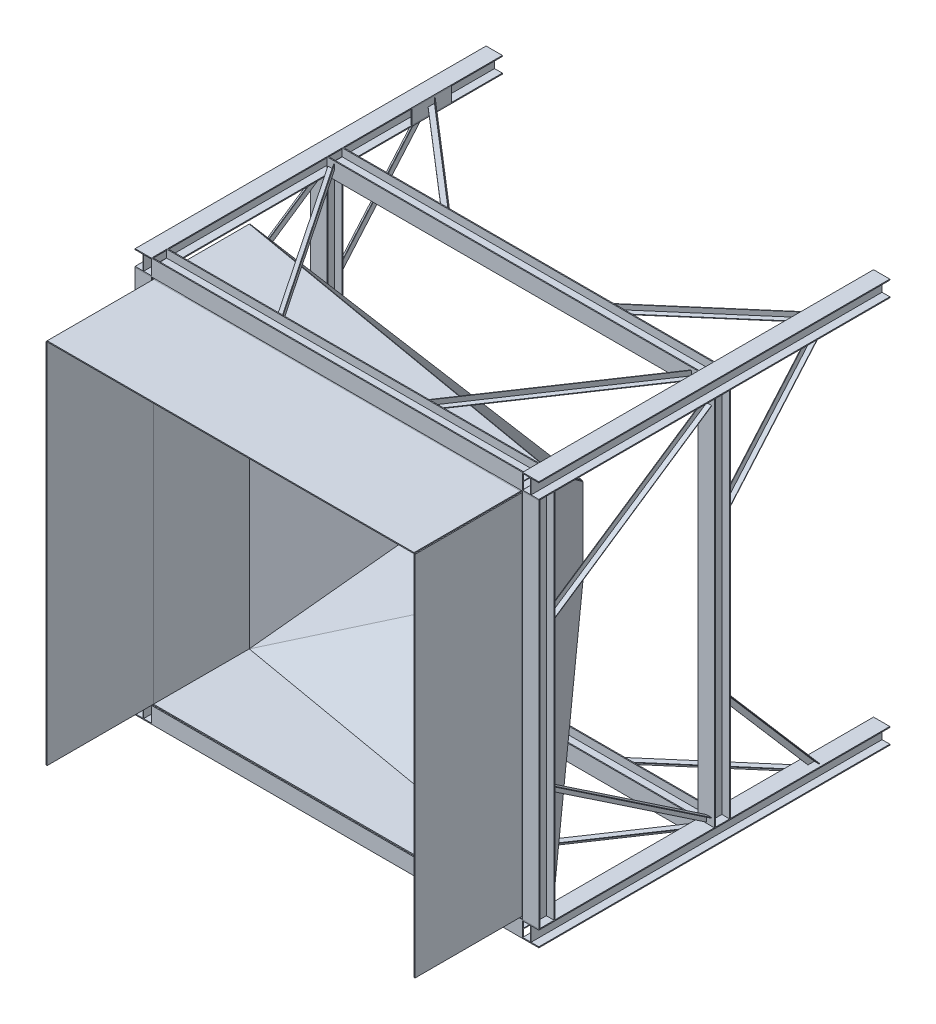
SolidWorks part; units mm, degrees
other "DetailItem1"
other "DetailItem2"
other "DetailItem3"
other "DetailItem4"
other "DetailItem5"
other "DetailItem6"
other "DetailItem7"
other "DetailItem8"
other "DetailItem9"
other "DetailItem10"
other "DetailItem11"
other "DetailItem12"
other "DetailItem13"
other "DetailItem14"
other "DetailItem15"
other "DetailItem16"
other "DetailItem17"
other "DetailItem18"
other "DetailItem19"
other "DetailItem20"
other "DetailItem21"
other "DetailItem22"
other "DetailItem23"
other "DetailItem24"
other "DetailItem25"
other "DetailItem26"
other "DetailItem27"
other "DetailItem28"
other "DetailItem29"
other "DetailItem30"
other "DetailItem31"
other "DetailItem32"
other "DetailItem33"
other "DetailItem34"
other "DetailItem35"
other "DetailItem36"
other "DetailItem37"
other "DetailItem38"
other "DetailItem39"
other "DetailItem40"
other "DetailItem41"
other "DetailItem42"
other "DetailItem43"
other "DetailItem44"
other "DetailItem45"
other "DetailItem46"
other "DetailItem47"
other "DetailItem48"
other "DetailItem49"
other "DetailItem50"
other "DetailItem51"
other "DetailItem52"
other "DetailItem53"
other "DetailItem54"
other "DetailItem55"
other "DetailItem56"
other "DetailItem57"
other "DetailItem58"
other "DetailItem59"
other "DetailItem60"
other "DetailItem61"
other "DetailItem62"
other "DetailItem63"
other "DetailItem64"
other "DetailItem65"
other "DetailItem66"
other "DetailItem67"
other "DetailItem68"
other "DetailItem69"
other "DetailItem70"
other "DetailItem71"
other "DetailItem72"
other "DetailItem73"
other "DetailItem74"
other "DetailItem75"
other "Carpeta de soldadura"
other "Cordón de soldadura1"
other "Soldadura Viga H carga 1650 B"
other "Soldadura Viga H carga 3300 A"
other "Soldadura Viga H carga 3300 B"
other "Soldadura asiento a tolva carga"
other "Soldadura asiento a bastidor carga"
other "Soldadura Viga H fondo 1650 A"
other "Soldadura Viga H fondo 1650 B"
other "Soldadura Viga H fondo 3300 A"
other "Soldadura Viga H fondo 3300 B"
other "Soldadura asiento a tolva fondo"
other "Soldadura asiento a bastidor fondo"
other "Soldadura Viga H izquierda 1650 A"
other "Soldadura Viga H izquierda 1650 B"
other "Soldadura Viga H izquierda 3300 A"
other "Soldadura Viga H izquierda 3300 B"
other "Soldadura asiento a tolva izquierda"
other "Soldadura asiento a bastidor izquierda"
other "Soldadura Viga H derecha 1650 A"
other "Soldadura Viga H derecha 1650 B"
other "Soldadura Viga H derecha 3300 A"
other "Soldadura Viga H derecha 3300 B"
other "Soldadura asiento a tolva derecha"
other "Soldadura asiento a bastidor derecha"
other "Soldadura Angular superior carga A inferior"
other "Soldadura Angular superior carga A superior"
other "Soldadura Angular inferior carga A inferior"
other "Soldadura Angular inferior carga A superior"
other "Soldadura Angular superior carga B inferior"
other "Soldadura Angular superior carga B superior"
other "Soldadura Angular inferior carga B inferior"
other "Soldadura Angular inferior carga B superior"
other "Soldadura Angular superior fondo A inferior"
other "Soldadura Angular superior fondo A superior"
other "Soldadura Angular inferior fondo A inferior"
other "Soldadura Angular inferior fondo A superior"
other "Soldadura Angular superior fondo B inferior"
other "Soldadura Angular superior fondo B superior"
other "Soldadura Angular inferior fondo B inferior"
other "Soldadura Angular inferior fondo B superior"
other "Soldadura Angular superior izquierda A inferior"
other "Soldadura Angular superior izquierda A superior"
other "Soldadura Angular inferior izquierda A inferior"
other "Soldadura Angular inferior izquierda A superior"
other "Soldadura Angular superior izquierda B inferior"
other "Soldadura Angular superior izquierda B superior"
other "Soldadura Angular inferior izquierda B inferior"
other "Soldadura Angular inferior izquierda B superior"
other "Soldadura Angular superior derecha A inferior"
other "Soldadura Angular superior derecha A superior"
other "Soldadura Angular inferior derecha A inferior"
other "Soldadura Angular inferior derecha A superior"
other "Soldadura Angular superior derecha B inferior"
other "Soldadura Angular superior derecha B superior"
other "Soldadura Angular inferior derecha B inferior"
other "Soldadura Angular inferior derecha B superior"
other "Soldadura esquina del collar carga"
other "Soldadura quiebre del embudo carga"
other "Soldadura arista inclinada carga"
other "Soldadura diagonal carga"
other "Soldadura alerón a collar derecha"
other "Soldadura esquina del collar derecha"
other "Soldadura quiebre del embudo derecha"
other "Soldadura arista inclinada derecha"
other "Soldadura alerón a collar fondo"
other "Soldadura esquina del collar fondo"
other "Soldadura quiebre del embudo fondo"
other "Soldadura arista inclinada fondo"
other "Soldadura diagonal fondo"
other "Soldadura alerón a collar izquierda"
other "Soldadura esquina del collar izquierda"
other "Soldadura quiebre del embudo izquierda"
other "Soldadura arista inclinada izquierda"
other "Soldadura esquina alerones derecha"
other "Soldadura esquina alerones izquierda"
material "ASTM A36 Steel"
ref_plane "Front Plane" through (0, 0, 0) normal (0, 0, 1) x (1, 0, 0)
ref_plane "Top Plane" through (0, 0, 0) normal (0, 1, 0) x (1, 0, 0)
ref_plane "Right Plane" through (0, 0, 0) normal (1, 0, 0) x (0, 0, -1)
sketch3d "Referencias 1"
  point P0 (0, 0, 0)
  point P1 (0, -190, 0)
  point P2 (200, 0, 0)
ref_plane "Plano de perfil 1 estructura" through (0, 0, 0) normal (0, 0, 1) x (1, 0, 0)
sketch "Contorno Columna H 1" plane through (0, 0, 0) normal (0, 0, 1) x (1, 0, 0)
  line L0 (-1898, -1898) -> (-1745, -1898)
  line L1 (-1745, -1898) -> (-1745, -1889)
  line L2 (-1745, -1889) -> (-1818.25, -1889)
  line L3 (-1818.25, -1889) -> (-1818.25, -1754)
  line L4 (-1818.25, -1754) -> (-1745, -1754)
  line L5 (-1745, -1754) -> (-1745, -1745)
  line L6 (-1745, -1745) -> (-1898, -1745)
  line L7 (-1898, -1745) -> (-1898, -1754)
  line L8 (-1898, -1754) -> (-1824.75, -1754)
  line L9 (-1824.75, -1754) -> (-1824.75, -1889)
  line L10 (-1824.75, -1889) -> (-1898, -1889)
  line L11 (-1898, -1889) -> (-1898, -1898)
extrude "Columna H 1" add sketch "Contorno Columna H 1" along normal blind 3300 separate body
sketch "Contorno Columna H 2" plane through (0, 0, 0) normal (0, 0, 1) x (1, 0, 0)
  line L0 (-1898, 1745) -> (-1745, 1745)
  line L1 (-1745, 1745) -> (-1745, 1754)
  line L2 (-1745, 1754) -> (-1818.25, 1754)
  line L3 (-1818.25, 1754) -> (-1818.25, 1889)
  line L4 (-1818.25, 1889) -> (-1745, 1889)
  line L5 (-1745, 1889) -> (-1745, 1898)
  line L6 (-1745, 1898) -> (-1898, 1898)
  line L7 (-1898, 1898) -> (-1898, 1889)
  line L8 (-1898, 1889) -> (-1824.75, 1889)
  line L9 (-1824.75, 1889) -> (-1824.75, 1754)
  line L10 (-1824.75, 1754) -> (-1898, 1754)
  line L11 (-1898, 1754) -> (-1898, 1745)
extrude "Columna H 2" add sketch "Contorno Columna H 2" along normal blind 3300 separate body
sketch "Contorno Columna H 3" plane through (0, 0, 0) normal (0, 0, 1) x (1, 0, 0)
  line L0 (1745, -1898) -> (1898, -1898)
  line L1 (1898, -1898) -> (1898, -1889)
  line L2 (1898, -1889) -> (1824.75, -1889)
  line L3 (1824.75, -1889) -> (1824.75, -1754)
  line L4 (1824.75, -1754) -> (1898, -1754)
  line L5 (1898, -1754) -> (1898, -1745)
  line L6 (1898, -1745) -> (1745, -1745)
  line L7 (1745, -1745) -> (1745, -1754)
  line L8 (1745, -1754) -> (1818.25, -1754)
  line L9 (1818.25, -1754) -> (1818.25, -1889)
  line L10 (1818.25, -1889) -> (1745, -1889)
  line L11 (1745, -1889) -> (1745, -1898)
extrude "Columna H 3" add sketch "Contorno Columna H 3" along normal blind 3300 separate body
sketch "Contorno Columna H 4" plane through (0, 0, 0) normal (0, 0, 1) x (1, 0, 0)
  line L0 (1745, 1745) -> (1898, 1745)
  line L1 (1898, 1745) -> (1898, 1754)
  line L2 (1898, 1754) -> (1824.75, 1754)
  line L3 (1824.75, 1754) -> (1824.75, 1889)
  line L4 (1824.75, 1889) -> (1898, 1889)
  line L5 (1898, 1889) -> (1898, 1898)
  line L6 (1898, 1898) -> (1745, 1898)
  line L7 (1745, 1898) -> (1745, 1889)
  line L8 (1745, 1889) -> (1818.25, 1889)
  line L9 (1818.25, 1889) -> (1818.25, 1754)
  line L10 (1818.25, 1754) -> (1745, 1754)
  line L11 (1745, 1754) -> (1745, 1745)
extrude "Columna H 4" add sketch "Contorno Columna H 4" along normal blind 3300 separate body
sketch3d "Referencias 2"
  point P0 (-1745, 0, 0)
  point P1 (-1745, 190, 0)
  point P2 (-1745, 0, 200)
ref_plane "Plano de perfil 2 estructura" through (-1745, 0, 0) normal (1, 0, 0) x (0, 0, -1)
sketch "Contorno Viga H carga 1650" plane through (-1745, 0, 0) normal (1, 0, 0) x (0, 0, -1)
  line L0 (-1497, -1745) -> (-1497, -1898)
  line L1 (-1497, -1898) -> (-1506, -1898)
  line L2 (-1506, -1898) -> (-1506, -1824.75)
  line L3 (-1506, -1824.75) -> (-1641, -1824.75)
  line L4 (-1641, -1824.75) -> (-1641, -1898)
  line L5 (-1641, -1898) -> (-1650, -1898)
  line L6 (-1650, -1898) -> (-1650, -1745)
  line L7 (-1650, -1745) -> (-1641, -1745)
  line L8 (-1641, -1745) -> (-1641, -1818.25)
  line L9 (-1641, -1818.25) -> (-1506, -1818.25)
  line L10 (-1506, -1818.25) -> (-1506, -1745)
  line L11 (-1506, -1745) -> (-1497, -1745)
extrude "Viga H carga 1650" add sketch "Contorno Viga H carga 1650" along normal blind 3490 separate body
sketch "Contorno Viga H carga 3300" plane through (-1745, 0, 0) normal (1, 0, 0) x (0, 0, -1)
  line L0 (-3147, -1745) -> (-3147, -1898)
  line L1 (-3147, -1898) -> (-3156, -1898)
  line L2 (-3156, -1898) -> (-3156, -1824.75)
  line L3 (-3156, -1824.75) -> (-3291, -1824.75)
  line L4 (-3291, -1824.75) -> (-3291, -1898)
  line L5 (-3291, -1898) -> (-3300, -1898)
  line L6 (-3300, -1898) -> (-3300, -1745)
  line L7 (-3300, -1745) -> (-3291, -1745)
  line L8 (-3291, -1745) -> (-3291, -1818.25)
  line L9 (-3291, -1818.25) -> (-3156, -1818.25)
  line L10 (-3156, -1818.25) -> (-3156, -1745)
  line L11 (-3156, -1745) -> (-3147, -1745)
extrude "Viga H carga 3300" add sketch "Contorno Viga H carga 3300" along normal blind 3490 separate body
sketch "Contorno Cierre columna carga A" plane through (-1745, 0, 0) normal (1, 0, 0) x (0, 0, -1)
  line L0 (-480, -1754) -> (-480, -1889)
  line L1 (-480, -1889) -> (-850, -1889)
  line L2 (-850, -1889) -> (-850, -1754)
  line L3 (-850, -1754) -> (-480, -1754)
extrude "Cierre columna carga A" add sketch "Contorno Cierre columna carga A" against normal blind 8 separate body
sketch3d "Referencias 3"
  point P0 (0, -1821.5, 0)
  point P1 (-190, -1821.5, 0)
  point P2 (0, -1821.5, 200)
ref_plane "Plano de perfil 3 estructura" through (0, -1821.5, 0) normal (0, 1, 0) x (1, 0, 0)
sketch "Contorno Ala plana Angular superior carga A" plane through (0, -1821.5, 0) normal (0, 1, 0) x (1, 0, 0)
  line L0 (-1674.8701, -1650) -> (-1735.1299, -1650)
  line L1 (-1735.1299, -1650) -> (-728.1299, -3147)
  line L2 (-728.1299, -3147) -> (-667.8701, -3147)
  line L3 (-667.8701, -3147) -> (-1674.8701, -1650)
extrude "Ala plana Angular superior carga A" add sketch "Contorno Ala plana Angular superior carga A" against normal blind 5 separate body
sketch3d "Referencias 4"
  point P0 (0, -1826.5, 0)
  point P1 (-190, -1826.5, 0)
  point P2 (0, -1826.5, 200)
ref_plane "Plano de perfil 4 estructura" through (0, -1826.5, 0) normal (0, 1, 0) x (1, 0, 0)
sketch "Contorno Retorno Angular superior carga A" plane through (0, -1826.5, 0) normal (0, 1, 0) x (1, 0, 0)
  line L0 (-1674.8701, -1650) -> (-1680.8961, -1650)
  line L1 (-1680.8961, -1650) -> (-673.8961, -3147)
  line L2 (-673.8961, -3147) -> (-667.8701, -3147)
  line L3 (-667.8701, -3147) -> (-1674.8701, -1650)
extrude "Retorno Angular superior carga A" add sketch "Contorno Retorno Angular superior carga A" against normal blind 45 separate body
combine bodies "Angular superior carga A" operation type add bodies to combine 108 109
sketch "Contorno Ala plana Angular inferior carga A" plane through (0, -1821.5, 0) normal (0, 1, 0) x (1, 0, 0)
  line L0 (-1745, -631.991) -> (-1745, -698.009)
  line L1 (-1745, -698.009) -> (-818.2856, -1497)
  line L2 (-818.2856, -1497) -> (-741.7144, -1497)
  line L3 (-741.7144, -1497) -> (-1745, -631.991)
extrude "Ala plana Angular inferior carga A" add sketch "Contorno Ala plana Angular inferior carga A" against normal blind 5 separate body
sketch "Contorno Retorno Angular inferior carga A" plane through (0, -1826.5, 0) normal (0, 1, 0) x (1, 0, 0)
  line L0 (-1745, -631.991) -> (-1745, -638.5928)
  line L1 (-1745, -638.5928) -> (-749.3715, -1497)
  line L2 (-749.3715, -1497) -> (-741.7144, -1497)
  line L3 (-741.7144, -1497) -> (-1745, -631.991)
extrude "Retorno Angular inferior carga A" add sketch "Contorno Retorno Angular inferior carga A" against normal blind 45 separate body
combine bodies "Angular inferior carga A" operation type add bodies to combine 111 112
sketch3d "Referencias 5"
  point P0 (1745, 0, 0)
  point P1 (1745, 190, 0)
  point P2 (1745, 0, 200)
ref_plane "Plano de perfil 5 estructura" through (1745, 0, 0) normal (1, 0, 0) x (0, 0, -1)
sketch "Contorno Cierre columna carga B" plane through (1745, 0, 0) normal (1, 0, 0) x (0, 0, -1)
  line L0 (-480, -1754) -> (-480, -1889)
  line L1 (-480, -1889) -> (-850, -1889)
  line L2 (-850, -1889) -> (-850, -1754)
  line L3 (-850, -1754) -> (-480, -1754)
extrude "Cierre columna carga B" add sketch "Contorno Cierre columna carga B" along normal blind 8 separate body
sketch "Contorno Ala plana Angular superior carga B" plane through (0, -1821.5, 0) normal (0, 1, 0) x (1, 0, 0)
  line L0 (1674.8701, -1650) -> (1735.1299, -1650)
  line L1 (1735.1299, -1650) -> (728.1299, -3147)
  line L2 (728.1299, -3147) -> (667.8701, -3147)
  line L3 (667.8701, -3147) -> (1674.8701, -1650)
extrude "Ala plana Angular superior carga B" add sketch "Contorno Ala plana Angular superior carga B" against normal blind 5 separate body
sketch "Contorno Retorno Angular superior carga B" plane through (0, -1826.5, 0) normal (0, 1, 0) x (1, 0, 0)
  line L0 (1674.8701, -1650) -> (1680.8961, -1650)
  line L1 (1680.8961, -1650) -> (673.8961, -3147)
  line L2 (673.8961, -3147) -> (667.8701, -3147)
  line L3 (667.8701, -3147) -> (1674.8701, -1650)
extrude "Retorno Angular superior carga B" add sketch "Contorno Retorno Angular superior carga B" against normal blind 45 separate body
combine bodies "Angular superior carga B" operation type add bodies to combine 115 116
sketch "Contorno Ala plana Angular inferior carga B" plane through (0, -1821.5, 0) normal (0, 1, 0) x (1, 0, 0)
  line L0 (1745, -631.991) -> (1745, -698.009)
  line L1 (1745, -698.009) -> (818.2856, -1497)
  line L2 (818.2856, -1497) -> (741.7144, -1497)
  line L3 (741.7144, -1497) -> (1745, -631.991)
extrude "Ala plana Angular inferior carga B" add sketch "Contorno Ala plana Angular inferior carga B" against normal blind 5 separate body
sketch "Contorno Retorno Angular inferior carga B" plane through (0, -1826.5, 0) normal (0, 1, 0) x (1, 0, 0)
  line L0 (1745, -631.991) -> (1745, -638.5928)
  line L1 (1745, -638.5928) -> (749.3715, -1497)
  line L2 (749.3715, -1497) -> (741.7144, -1497)
  line L3 (741.7144, -1497) -> (1745, -631.991)
extrude "Retorno Angular inferior carga B" add sketch "Contorno Retorno Angular inferior carga B" against normal blind 45 separate body
combine bodies "Angular inferior carga B" operation type add bodies to combine 118 119
sketch3d "Referencias 6"
  point P0 (0, 0, 3281.475)
  point P1 (0, -190, 3281.475)
  point P2 (200, 0, 3281.475)
ref_plane "Plano de perfil 6 estructura" through (0, 0, 3281.475) normal (0, 0, 1) x (1, 0, 0)
sketch "Contorno Asiento soldado carga" plane through (0, 0, 3281.475) normal (0, 0, 1) x (1, 0, 0)
  line L0 (-1450, -1734.525) -> (1450, -1734.525)
  line L1 (1450, -1734.525) -> (1450, -1818.25)
  line L2 (1450, -1818.25) -> (-1450, -1818.25)
  line L3 (-1450, -1818.25) -> (-1450, -1734.525)
extrude "Asiento soldado carga" add sketch "Contorno Asiento soldado carga" along normal blind 9.525 separate body
sketch "Contorno Viga H fondo 1650" plane through (-1745, 0, 0) normal (1, 0, 0) x (0, 0, -1)
  line L0 (-1497, 1745) -> (-1497, 1898)
  line L1 (-1497, 1898) -> (-1506, 1898)
  line L2 (-1506, 1898) -> (-1506, 1824.75)
  line L3 (-1506, 1824.75) -> (-1641, 1824.75)
  line L4 (-1641, 1824.75) -> (-1641, 1898)
  line L5 (-1641, 1898) -> (-1650, 1898)
  line L6 (-1650, 1898) -> (-1650, 1745)
  line L7 (-1650, 1745) -> (-1641, 1745)
  line L8 (-1641, 1745) -> (-1641, 1818.25)
  line L9 (-1641, 1818.25) -> (-1506, 1818.25)
  line L10 (-1506, 1818.25) -> (-1506, 1745)
  line L11 (-1506, 1745) -> (-1497, 1745)
extrude "Viga H fondo 1650" add sketch "Contorno Viga H fondo 1650" along normal blind 3490 separate body
sketch "Contorno Viga H fondo 3300" plane through (-1745, 0, 0) normal (1, 0, 0) x (0, 0, -1)
  line L0 (-3147, 1745) -> (-3147, 1898)
  line L1 (-3147, 1898) -> (-3156, 1898)
  line L2 (-3156, 1898) -> (-3156, 1824.75)
  line L3 (-3156, 1824.75) -> (-3291, 1824.75)
  line L4 (-3291, 1824.75) -> (-3291, 1898)
  line L5 (-3291, 1898) -> (-3300, 1898)
  line L6 (-3300, 1898) -> (-3300, 1745)
  line L7 (-3300, 1745) -> (-3291, 1745)
  line L8 (-3291, 1745) -> (-3291, 1818.25)
  line L9 (-3291, 1818.25) -> (-3156, 1818.25)
  line L10 (-3156, 1818.25) -> (-3156, 1745)
  line L11 (-3156, 1745) -> (-3147, 1745)
extrude "Viga H fondo 3300" add sketch "Contorno Viga H fondo 3300" along normal blind 3490 separate body
sketch "Contorno Cierre columna fondo A" plane through (-1745, 0, 0) normal (1, 0, 0) x (0, 0, -1)
  line L0 (-480, 1754) -> (-480, 1889)
  line L1 (-480, 1889) -> (-850, 1889)
  line L2 (-850, 1889) -> (-850, 1754)
  line L3 (-850, 1754) -> (-480, 1754)
extrude "Cierre columna fondo A" add sketch "Contorno Cierre columna fondo A" against normal blind 8 separate body
sketch3d "Referencias 7"
  point P0 (0, 1821.5, 0)
  point P1 (-190, 1821.5, 0)
  point P2 (0, 1821.5, 200)
ref_plane "Plano de perfil 7 estructura" through (0, 1821.5, 0) normal (0, 1, 0) x (1, 0, 0)
sketch "Contorno Ala plana Angular superior fondo A" plane through (0, 1821.5, 0) normal (0, 1, 0) x (1, 0, 0)
  line L0 (-1674.8701, -1650) -> (-1735.1299, -1650)
  line L1 (-1735.1299, -1650) -> (-728.1299, -3147)
  line L2 (-728.1299, -3147) -> (-667.8701, -3147)
  line L3 (-667.8701, -3147) -> (-1674.8701, -1650)
extrude "Ala plana Angular superior fondo A" add sketch "Contorno Ala plana Angular superior fondo A" along normal blind 5 separate body
sketch3d "Referencias 8"
  point P0 (0, 1826.5, 0)
  point P1 (-190, 1826.5, 0)
  point P2 (0, 1826.5, 200)
ref_plane "Plano de perfil 8 estructura" through (0, 1826.5, 0) normal (0, 1, 0) x (1, 0, 0)
sketch "Contorno Retorno Angular superior fondo A" plane through (0, 1826.5, 0) normal (0, 1, 0) x (1, 0, 0)
  line L0 (-1674.8701, -1650) -> (-1680.8961, -1650)
  line L1 (-1680.8961, -1650) -> (-673.8961, -3147)
  line L2 (-673.8961, -3147) -> (-667.8701, -3147)
  line L3 (-667.8701, -3147) -> (-1674.8701, -1650)
extrude "Retorno Angular superior fondo A" add sketch "Contorno Retorno Angular superior fondo A" along normal blind 45 separate body
combine bodies "Angular superior fondo A" operation type add bodies to combine 125 126
sketch "Contorno Ala plana Angular inferior fondo A" plane through (0, 1821.5, 0) normal (0, 1, 0) x (1, 0, 0)
  line L0 (-1745, -631.991) -> (-1745, -698.009)
  line L1 (-1745, -698.009) -> (-818.2856, -1497)
  line L2 (-818.2856, -1497) -> (-741.7144, -1497)
  line L3 (-741.7144, -1497) -> (-1745, -631.991)
extrude "Ala plana Angular inferior fondo A" add sketch "Contorno Ala plana Angular inferior fondo A" along normal blind 5 separate body
sketch "Contorno Retorno Angular inferior fondo A" plane through (0, 1826.5, 0) normal (0, 1, 0) x (1, 0, 0)
  line L0 (-1745, -631.991) -> (-1745, -638.5928)
  line L1 (-1745, -638.5928) -> (-749.3715, -1497)
  line L2 (-749.3715, -1497) -> (-741.7144, -1497)
  line L3 (-741.7144, -1497) -> (-1745, -631.991)
extrude "Retorno Angular inferior fondo A" add sketch "Contorno Retorno Angular inferior fondo A" along normal blind 45 separate body
combine bodies "Angular inferior fondo A" operation type add bodies to combine 128 129
sketch "Contorno Cierre columna fondo B" plane through (1745, 0, 0) normal (1, 0, 0) x (0, 0, -1)
  line L0 (-480, 1754) -> (-480, 1889)
  line L1 (-480, 1889) -> (-850, 1889)
  line L2 (-850, 1889) -> (-850, 1754)
  line L3 (-850, 1754) -> (-480, 1754)
extrude "Cierre columna fondo B" add sketch "Contorno Cierre columna fondo B" along normal blind 8 separate body
sketch "Contorno Ala plana Angular superior fondo B" plane through (0, 1821.5, 0) normal (0, 1, 0) x (1, 0, 0)
  line L0 (1674.8701, -1650) -> (1735.1299, -1650)
  line L1 (1735.1299, -1650) -> (728.1299, -3147)
  line L2 (728.1299, -3147) -> (667.8701, -3147)
  line L3 (667.8701, -3147) -> (1674.8701, -1650)
extrude "Ala plana Angular superior fondo B" add sketch "Contorno Ala plana Angular superior fondo B" along normal blind 5 separate body
sketch "Contorno Retorno Angular superior fondo B" plane through (0, 1826.5, 0) normal (0, 1, 0) x (1, 0, 0)
  line L0 (1674.8701, -1650) -> (1680.8961, -1650)
  line L1 (1680.8961, -1650) -> (673.8961, -3147)
  line L2 (673.8961, -3147) -> (667.8701, -3147)
  line L3 (667.8701, -3147) -> (1674.8701, -1650)
extrude "Retorno Angular superior fondo B" add sketch "Contorno Retorno Angular superior fondo B" along normal blind 45 separate body
combine bodies "Angular superior fondo B" operation type add bodies to combine 132 133
sketch "Contorno Ala plana Angular inferior fondo B" plane through (0, 1821.5, 0) normal (0, 1, 0) x (1, 0, 0)
  line L0 (1745, -631.991) -> (1745, -698.009)
  line L1 (1745, -698.009) -> (818.2856, -1497)
  line L2 (818.2856, -1497) -> (741.7144, -1497)
  line L3 (741.7144, -1497) -> (1745, -631.991)
extrude "Ala plana Angular inferior fondo B" add sketch "Contorno Ala plana Angular inferior fondo B" along normal blind 5 separate body
sketch "Contorno Retorno Angular inferior fondo B" plane through (0, 1826.5, 0) normal (0, 1, 0) x (1, 0, 0)
  line L0 (1745, -631.991) -> (1745, -638.5928)
  line L1 (1745, -638.5928) -> (749.3715, -1497)
  line L2 (749.3715, -1497) -> (741.7144, -1497)
  line L3 (741.7144, -1497) -> (1745, -631.991)
extrude "Retorno Angular inferior fondo B" add sketch "Contorno Retorno Angular inferior fondo B" along normal blind 45 separate body
combine bodies "Angular inferior fondo B" operation type add bodies to combine 135 136
sketch "Contorno Asiento soldado fondo" plane through (0, 0, 3281.475) normal (0, 0, 1) x (1, 0, 0)
  line L0 (-1450, 1734.525) -> (1450, 1734.525)
  line L1 (1450, 1734.525) -> (1450, 1818.25)
  line L2 (1450, 1818.25) -> (-1450, 1818.25)
  line L3 (-1450, 1818.25) -> (-1450, 1734.525)
extrude "Asiento soldado fondo" add sketch "Contorno Asiento soldado fondo" along normal blind 9.525 separate body
sketch3d "Referencias 9"
  point P0 (0, -1745, 0)
  point P1 (-190, -1745, 0)
  point P2 (0, -1745, 200)
ref_plane "Plano de perfil 9 estructura" through (0, -1745, 0) normal (0, 1, 0) x (1, 0, 0)
sketch "Contorno Viga H izquierda 1650" plane through (0, -1745, 0) normal (0, 1, 0) x (1, 0, 0)
  line L0 (-1745, -1497) -> (-1898, -1497)
  line L1 (-1898, -1497) -> (-1898, -1506)
  line L2 (-1898, -1506) -> (-1824.75, -1506)
  line L3 (-1824.75, -1506) -> (-1824.75, -1641)
  line L4 (-1824.75, -1641) -> (-1898, -1641)
  line L5 (-1898, -1641) -> (-1898, -1650)
  line L6 (-1898, -1650) -> (-1745, -1650)
  line L7 (-1745, -1650) -> (-1745, -1641)
  line L8 (-1745, -1641) -> (-1818.25, -1641)
  line L9 (-1818.25, -1641) -> (-1818.25, -1506)
  line L10 (-1818.25, -1506) -> (-1745, -1506)
  line L11 (-1745, -1506) -> (-1745, -1497)
extrude "Viga H izquierda 1650" add sketch "Contorno Viga H izquierda 1650" along normal blind 3490 separate body
sketch "Contorno Viga H izquierda 3300" plane through (0, -1745, 0) normal (0, 1, 0) x (1, 0, 0)
  line L0 (-1745, -3147) -> (-1898, -3147)
  line L1 (-1898, -3147) -> (-1898, -3156)
  line L2 (-1898, -3156) -> (-1824.75, -3156)
  line L3 (-1824.75, -3156) -> (-1824.75, -3291)
  line L4 (-1824.75, -3291) -> (-1898, -3291)
  line L5 (-1898, -3291) -> (-1898, -3300)
  line L6 (-1898, -3300) -> (-1745, -3300)
  line L7 (-1745, -3300) -> (-1745, -3291)
  line L8 (-1745, -3291) -> (-1818.25, -3291)
  line L9 (-1818.25, -3291) -> (-1818.25, -3156)
  line L10 (-1818.25, -3156) -> (-1745, -3156)
  line L11 (-1745, -3156) -> (-1745, -3147)
extrude "Viga H izquierda 3300" add sketch "Contorno Viga H izquierda 3300" along normal blind 3490 separate body
sketch3d "Referencias 10"
  point P0 (-1821.5, 0, 0)
  point P1 (-1821.5, 190, 0)
  point P2 (-1821.5, 0, 200)
ref_plane "Plano de perfil 10 estructura" through (-1821.5, 0, 0) normal (1, 0, 0) x (0, 0, -1)
sketch "Contorno Ala plana Angular superior izquierda A" plane through (-1821.5, 0, 0) normal (1, 0, 0) x (0, 0, -1)
  line L0 (-1650, -1674.8701) -> (-1650, -1735.1299)
  line L1 (-1650, -1735.1299) -> (-3147, -728.1299)
  line L2 (-3147, -728.1299) -> (-3147, -667.8701)
  line L3 (-3147, -667.8701) -> (-1650, -1674.8701)
extrude "Ala plana Angular superior izquierda A" add sketch "Contorno Ala plana Angular superior izquierda A" against normal blind 5 separate body
sketch3d "Referencias 11"
  point P0 (-1826.5, 0, 0)
  point P1 (-1826.5, 190, 0)
  point P2 (-1826.5, 0, 200)
ref_plane "Plano de perfil 11 estructura" through (-1826.5, 0, 0) normal (1, 0, 0) x (0, 0, -1)
sketch "Contorno Retorno Angular superior izquierda A" plane through (-1826.5, 0, 0) normal (1, 0, 0) x (0, 0, -1)
  line L0 (-1650, -1674.8701) -> (-1650, -1680.8961)
  line L1 (-1650, -1680.8961) -> (-3147, -673.8961)
  line L2 (-3147, -673.8961) -> (-3147, -667.8701)
  line L3 (-3147, -667.8701) -> (-1650, -1674.8701)
extrude "Retorno Angular superior izquierda A" add sketch "Contorno Retorno Angular superior izquierda A" against normal blind 45 separate body
combine bodies "Angular superior izquierda A" operation type add bodies to combine 141 142
sketch "Contorno Ala plana Angular inferior izquierda A" plane through (-1821.5, 0, 0) normal (1, 0, 0) x (0, 0, -1)
  line L0 (-631.991, -1745) -> (-698.009, -1745)
  line L1 (-698.009, -1745) -> (-1497, -818.2856)
  line L2 (-1497, -818.2856) -> (-1497, -741.7144)
  line L3 (-1497, -741.7144) -> (-631.991, -1745)
extrude "Ala plana Angular inferior izquierda A" add sketch "Contorno Ala plana Angular inferior izquierda A" against normal blind 5 separate body
sketch "Contorno Retorno Angular inferior izquierda A" plane through (-1826.5, 0, 0) normal (1, 0, 0) x (0, 0, -1)
  line L0 (-631.991, -1745) -> (-638.5928, -1745)
  line L1 (-638.5928, -1745) -> (-1497, -749.3715)
  line L2 (-1497, -749.3715) -> (-1497, -741.7144)
  line L3 (-1497, -741.7144) -> (-631.991, -1745)
extrude "Retorno Angular inferior izquierda A" add sketch "Contorno Retorno Angular inferior izquierda A" against normal blind 45 separate body
combine bodies "Angular inferior izquierda A" operation type add bodies to combine 144 145
sketch "Contorno Ala plana Angular superior izquierda B" plane through (-1821.5, 0, 0) normal (1, 0, 0) x (0, 0, -1)
  line L0 (-1650, 1674.8701) -> (-1650, 1735.1299)
  line L1 (-1650, 1735.1299) -> (-3147, 728.1299)
  line L2 (-3147, 728.1299) -> (-3147, 667.8701)
  line L3 (-3147, 667.8701) -> (-1650, 1674.8701)
extrude "Ala plana Angular superior izquierda B" add sketch "Contorno Ala plana Angular superior izquierda B" against normal blind 5 separate body
sketch "Contorno Retorno Angular superior izquierda B" plane through (-1826.5, 0, 0) normal (1, 0, 0) x (0, 0, -1)
  line L0 (-1650, 1674.8701) -> (-1650, 1680.8961)
  line L1 (-1650, 1680.8961) -> (-3147, 673.8961)
  line L2 (-3147, 673.8961) -> (-3147, 667.8701)
  line L3 (-3147, 667.8701) -> (-1650, 1674.8701)
extrude "Retorno Angular superior izquierda B" add sketch "Contorno Retorno Angular superior izquierda B" against normal blind 45 separate body
combine bodies "Angular superior izquierda B" operation type add bodies to combine 147 148
sketch "Contorno Ala plana Angular inferior izquierda B" plane through (-1821.5, 0, 0) normal (1, 0, 0) x (0, 0, -1)
  line L0 (-631.991, 1745) -> (-698.009, 1745)
  line L1 (-698.009, 1745) -> (-1497, 818.2856)
  line L2 (-1497, 818.2856) -> (-1497, 741.7144)
  line L3 (-1497, 741.7144) -> (-631.991, 1745)
extrude "Ala plana Angular inferior izquierda B" add sketch "Contorno Ala plana Angular inferior izquierda B" against normal blind 5 separate body
sketch "Contorno Retorno Angular inferior izquierda B" plane through (-1826.5, 0, 0) normal (1, 0, 0) x (0, 0, -1)
  line L0 (-631.991, 1745) -> (-638.5928, 1745)
  line L1 (-638.5928, 1745) -> (-1497, 749.3715)
  line L2 (-1497, 749.3715) -> (-1497, 741.7144)
  line L3 (-1497, 741.7144) -> (-631.991, 1745)
extrude "Retorno Angular inferior izquierda B" add sketch "Contorno Retorno Angular inferior izquierda B" against normal blind 45 separate body
combine bodies "Angular inferior izquierda B" operation type add bodies to combine 150 151
sketch "Contorno Asiento soldado izquierda" plane through (0, 0, 3281.475) normal (0, 0, 1) x (1, 0, 0)
  line L0 (-1734.525, -1450) -> (-1734.525, 1450)
  line L1 (-1734.525, 1450) -> (-1818.25, 1450)
  line L2 (-1818.25, 1450) -> (-1818.25, -1450)
  line L3 (-1818.25, -1450) -> (-1734.525, -1450)
extrude "Asiento soldado izquierda" add sketch "Contorno Asiento soldado izquierda" along normal blind 9.525 separate body
sketch "Contorno Viga H derecha 1650" plane through (0, -1745, 0) normal (0, 1, 0) x (1, 0, 0)
  line L0 (1745, -1497) -> (1898, -1497)
  line L1 (1898, -1497) -> (1898, -1506)
  line L2 (1898, -1506) -> (1824.75, -1506)
  line L3 (1824.75, -1506) -> (1824.75, -1641)
  line L4 (1824.75, -1641) -> (1898, -1641)
  line L5 (1898, -1641) -> (1898, -1650)
  line L6 (1898, -1650) -> (1745, -1650)
  line L7 (1745, -1650) -> (1745, -1641)
  line L8 (1745, -1641) -> (1818.25, -1641)
  line L9 (1818.25, -1641) -> (1818.25, -1506)
  line L10 (1818.25, -1506) -> (1745, -1506)
  line L11 (1745, -1506) -> (1745, -1497)
extrude "Viga H derecha 1650" add sketch "Contorno Viga H derecha 1650" along normal blind 3490 separate body
sketch "Contorno Viga H derecha 3300" plane through (0, -1745, 0) normal (0, 1, 0) x (1, 0, 0)
  line L0 (1745, -3147) -> (1898, -3147)
  line L1 (1898, -3147) -> (1898, -3156)
  line L2 (1898, -3156) -> (1824.75, -3156)
  line L3 (1824.75, -3156) -> (1824.75, -3291)
  line L4 (1824.75, -3291) -> (1898, -3291)
  line L5 (1898, -3291) -> (1898, -3300)
  line L6 (1898, -3300) -> (1745, -3300)
  line L7 (1745, -3300) -> (1745, -3291)
  line L8 (1745, -3291) -> (1818.25, -3291)
  line L9 (1818.25, -3291) -> (1818.25, -3156)
  line L10 (1818.25, -3156) -> (1745, -3156)
  line L11 (1745, -3156) -> (1745, -3147)
extrude "Viga H derecha 3300" add sketch "Contorno Viga H derecha 3300" along normal blind 3490 separate body
sketch3d "Referencias 12"
  point P0 (1821.5, 0, 0)
  point P1 (1821.5, 190, 0)
  point P2 (1821.5, 0, 200)
ref_plane "Plano de perfil 12 estructura" through (1821.5, 0, 0) normal (1, 0, 0) x (0, 0, -1)
sketch "Contorno Ala plana Angular superior derecha A" plane through (1821.5, 0, 0) normal (1, 0, 0) x (0, 0, -1)
  line L0 (-1650, -1674.8701) -> (-1650, -1735.1299)
  line L1 (-1650, -1735.1299) -> (-3147, -728.1299)
  line L2 (-3147, -728.1299) -> (-3147, -667.8701)
  line L3 (-3147, -667.8701) -> (-1650, -1674.8701)
extrude "Ala plana Angular superior derecha A" add sketch "Contorno Ala plana Angular superior derecha A" along normal blind 5 separate body
sketch3d "Referencias 13"
  point P0 (1826.5, 0, 0)
  point P1 (1826.5, 190, 0)
  point P2 (1826.5, 0, 200)
ref_plane "Plano de perfil 13 estructura" through (1826.5, 0, 0) normal (1, 0, 0) x (0, 0, -1)
sketch "Contorno Retorno Angular superior derecha A" plane through (1826.5, 0, 0) normal (1, 0, 0) x (0, 0, -1)
  line L0 (-1650, -1674.8701) -> (-1650, -1680.8961)
  line L1 (-1650, -1680.8961) -> (-3147, -673.8961)
  line L2 (-3147, -673.8961) -> (-3147, -667.8701)
  line L3 (-3147, -667.8701) -> (-1650, -1674.8701)
extrude "Retorno Angular superior derecha A" add sketch "Contorno Retorno Angular superior derecha A" along normal blind 45 separate body
combine bodies "Angular superior derecha A" operation type add bodies to combine 156 157
sketch "Contorno Ala plana Angular inferior derecha A" plane through (1821.5, 0, 0) normal (1, 0, 0) x (0, 0, -1)
  line L0 (-631.991, -1745) -> (-698.009, -1745)
  line L1 (-698.009, -1745) -> (-1497, -818.2856)
  line L2 (-1497, -818.2856) -> (-1497, -741.7144)
  line L3 (-1497, -741.7144) -> (-631.991, -1745)
extrude "Ala plana Angular inferior derecha A" add sketch "Contorno Ala plana Angular inferior derecha A" along normal blind 5 separate body
sketch "Contorno Retorno Angular inferior derecha A" plane through (1826.5, 0, 0) normal (1, 0, 0) x (0, 0, -1)
  line L0 (-631.991, -1745) -> (-638.5928, -1745)
  line L1 (-638.5928, -1745) -> (-1497, -749.3715)
  line L2 (-1497, -749.3715) -> (-1497, -741.7144)
  line L3 (-1497, -741.7144) -> (-631.991, -1745)
extrude "Retorno Angular inferior derecha A" add sketch "Contorno Retorno Angular inferior derecha A" along normal blind 45 separate body
combine bodies "Angular inferior derecha A" operation type add bodies to combine 159 160
sketch "Contorno Ala plana Angular superior derecha B" plane through (1821.5, 0, 0) normal (1, 0, 0) x (0, 0, -1)
  line L0 (-1650, 1674.8701) -> (-1650, 1735.1299)
  line L1 (-1650, 1735.1299) -> (-3147, 728.1299)
  line L2 (-3147, 728.1299) -> (-3147, 667.8701)
  line L3 (-3147, 667.8701) -> (-1650, 1674.8701)
extrude "Ala plana Angular superior derecha B" add sketch "Contorno Ala plana Angular superior derecha B" along normal blind 5 separate body
sketch "Contorno Retorno Angular superior derecha B" plane through (1826.5, 0, 0) normal (1, 0, 0) x (0, 0, -1)
  line L0 (-1650, 1674.8701) -> (-1650, 1680.8961)
  line L1 (-1650, 1680.8961) -> (-3147, 673.8961)
  line L2 (-3147, 673.8961) -> (-3147, 667.8701)
  line L3 (-3147, 667.8701) -> (-1650, 1674.8701)
extrude "Retorno Angular superior derecha B" add sketch "Contorno Retorno Angular superior derecha B" along normal blind 45 separate body
combine bodies "Angular superior derecha B" operation type add bodies to combine 162 163
sketch "Contorno Ala plana Angular inferior derecha B" plane through (1821.5, 0, 0) normal (1, 0, 0) x (0, 0, -1)
  line L0 (-631.991, 1745) -> (-698.009, 1745)
  line L1 (-698.009, 1745) -> (-1497, 818.2856)
  line L2 (-1497, 818.2856) -> (-1497, 741.7144)
  line L3 (-1497, 741.7144) -> (-631.991, 1745)
extrude "Ala plana Angular inferior derecha B" add sketch "Contorno Ala plana Angular inferior derecha B" along normal blind 5 separate body
sketch "Contorno Retorno Angular inferior derecha B" plane through (1826.5, 0, 0) normal (1, 0, 0) x (0, 0, -1)
  line L0 (-631.991, 1745) -> (-638.5928, 1745)
  line L1 (-638.5928, 1745) -> (-1497, 749.3715)
  line L2 (-1497, 749.3715) -> (-1497, 741.7144)
  line L3 (-1497, 741.7144) -> (-631.991, 1745)
extrude "Retorno Angular inferior derecha B" add sketch "Contorno Retorno Angular inferior derecha B" along normal blind 45 separate body
combine bodies "Angular inferior derecha B" operation type add bodies to combine 165 166
sketch "Contorno Asiento soldado derecha" plane through (0, 0, 3281.475) normal (0, 0, 1) x (1, 0, 0)
  line L0 (1734.525, -1450) -> (1734.525, 1450)
  line L1 (1734.525, 1450) -> (1818.25, 1450)
  line L2 (1818.25, 1450) -> (1818.25, -1450)
  line L3 (1818.25, -1450) -> (1734.525, -1450)
extrude "Asiento soldado derecha" add sketch "Contorno Asiento soldado derecha" along normal blind 9.525 separate body
sketch3d "Junta Viga H carga 1650 A"
  line L0 (-1745, -1745, 1650) -> (-1745, -1898, 1650)
sketch3d "Junta Viga H carga 1650 B"
  line L0 (1745, -1745, 1650) -> (1745, -1898, 1650)
sketch3d "Junta Viga H carga 3300 A"
  line L0 (-1745, -1745, 3300) -> (-1745, -1898, 3300)
sketch3d "Junta Viga H carga 3300 B"
  line L0 (1745, -1745, 3300) -> (1745, -1898, 3300)
sketch3d "Junta Angular superior carga A inferior"
  line L0 (-1674.8701, -1821.5, 1650) -> (-1735.1299, -1821.5, 1650)
sketch3d "Junta Angular superior carga A superior"
  line L0 (-667.8701, -1821.5, 3147) -> (-728.1299, -1821.5, 3147)
sketch3d "Junta Angular inferior carga A inferior"
  line L0 (-1745, -1821.5, 631.991) -> (-1745, -1821.5, 698.009)
sketch3d "Junta Angular inferior carga A superior"
  line L0 (-741.7144, -1821.5, 1497) -> (-818.2856, -1821.5, 1497)
sketch3d "Junta Angular superior carga B inferior"
  line L0 (1674.8701, -1821.5, 1650) -> (1735.1299, -1821.5, 1650)
sketch3d "Junta Angular superior carga B superior"
  line L0 (667.8701, -1821.5, 3147) -> (728.1299, -1821.5, 3147)
sketch3d "Junta Angular inferior carga B inferior"
  line L0 (1745, -1821.5, 631.991) -> (1745, -1821.5, 698.009)
sketch3d "Junta Angular inferior carga B superior"
  line L0 (741.7144, -1821.5, 1497) -> (818.2856, -1821.5, 1497)
sketch3d "Junta asiento a tolva carga"
  line L0 (-1450, -1734.525, 3281.475) -> (1450, -1734.525, 3281.475)
sketch3d "Junta asiento a bastidor carga"
  line L0 (-1450, -1745, 3291) -> (1450, -1745, 3291)
sketch3d "Junta Viga H fondo 1650 A"
  line L0 (-1745, 1745, 1650) -> (-1745, 1898, 1650)
sketch3d "Junta Viga H fondo 1650 B"
  line L0 (1745, 1745, 1650) -> (1745, 1898, 1650)
sketch3d "Junta Viga H fondo 3300 A"
  line L0 (-1745, 1745, 3300) -> (-1745, 1898, 3300)
sketch3d "Junta Viga H fondo 3300 B"
  line L0 (1745, 1745, 3300) -> (1745, 1898, 3300)
sketch3d "Junta Angular superior fondo A inferior"
  line L0 (-1674.8701, 1821.5, 1650) -> (-1735.1299, 1821.5, 1650)
sketch3d "Junta Angular superior fondo A superior"
  line L0 (-667.8701, 1821.5, 3147) -> (-728.1299, 1821.5, 3147)
sketch3d "Junta Angular inferior fondo A inferior"
  line L0 (-1745, 1821.5, 631.991) -> (-1745, 1821.5, 698.009)
sketch3d "Junta Angular inferior fondo A superior"
  line L0 (-741.7144, 1821.5, 1497) -> (-818.2856, 1821.5, 1497)
sketch3d "Junta Angular superior fondo B inferior"
  line L0 (1674.8701, 1821.5, 1650) -> (1735.1299, 1821.5, 1650)
sketch3d "Junta Angular superior fondo B superior"
  line L0 (667.8701, 1821.5, 3147) -> (728.1299, 1821.5, 3147)
sketch3d "Junta Angular inferior fondo B inferior"
  line L0 (1745, 1821.5, 631.991) -> (1745, 1821.5, 698.009)
sketch3d "Junta Angular inferior fondo B superior"
  line L0 (741.7144, 1821.5, 1497) -> (818.2856, 1821.5, 1497)
sketch3d "Junta asiento a tolva fondo"
  line L0 (-1450, 1734.525, 3281.475) -> (1450, 1734.525, 3281.475)
sketch3d "Junta asiento a bastidor fondo"
  line L0 (-1450, 1745, 3291) -> (1450, 1745, 3291)
sketch3d "Junta Viga H izquierda 1650 A"
  line L0 (-1745, -1745, 1650) -> (-1898, -1745, 1650)
sketch3d "Junta Viga H izquierda 1650 B"
  line L0 (-1745, 1745, 1650) -> (-1898, 1745, 1650)
sketch3d "Junta Viga H izquierda 3300 A"
  line L0 (-1745, -1745, 3300) -> (-1898, -1745, 3300)
sketch3d "Junta Viga H izquierda 3300 B"
  line L0 (-1745, 1745, 3300) -> (-1898, 1745, 3300)
sketch3d "Junta Angular superior izquierda A inferior"
  line L0 (-1821.5, -1674.8701, 1650) -> (-1821.5, -1735.1299, 1650)
sketch3d "Junta Angular superior izquierda A superior"
  line L0 (-1821.5, -667.8701, 3147) -> (-1821.5, -728.1299, 3147)
sketch3d "Junta Angular inferior izquierda A inferior"
  line L0 (-1821.5, -1745, 631.991) -> (-1821.5, -1745, 698.009)
sketch3d "Junta Angular inferior izquierda A superior"
  line L0 (-1821.5, -741.7144, 1497) -> (-1821.5, -818.2856, 1497)
sketch3d "Junta Angular superior izquierda B inferior"
  line L0 (-1821.5, 1674.8701, 1650) -> (-1821.5, 1735.1299, 1650)
sketch3d "Junta Angular superior izquierda B superior"
  line L0 (-1821.5, 667.8701, 3147) -> (-1821.5, 728.1299, 3147)
sketch3d "Junta Angular inferior izquierda B inferior"
  line L0 (-1821.5, 1745, 631.991) -> (-1821.5, 1745, 698.009)
sketch3d "Junta Angular inferior izquierda B superior"
  line L0 (-1821.5, 741.7144, 1497) -> (-1821.5, 818.2856, 1497)
sketch3d "Junta asiento a tolva izquierda"
  line L0 (-1734.525, -1450, 3281.475) -> (-1734.525, 1450, 3281.475)
sketch3d "Junta asiento a bastidor izquierda"
  line L0 (-1745, -1450, 3291) -> (-1745, 1450, 3291)
sketch3d "Junta Viga H derecha 1650 A"
  line L0 (1745, -1745, 1650) -> (1898, -1745, 1650)
sketch3d "Junta Viga H derecha 1650 B"
  line L0 (1745, 1745, 1650) -> (1898, 1745, 1650)
sketch3d "Junta Viga H derecha 3300 A"
  line L0 (1745, -1745, 3300) -> (1898, -1745, 3300)
sketch3d "Junta Viga H derecha 3300 B"
  line L0 (1745, 1745, 3300) -> (1898, 1745, 3300)
sketch3d "Junta Angular superior derecha A inferior"
  line L0 (1821.5, -1674.8701, 1650) -> (1821.5, -1735.1299, 1650)
sketch3d "Junta Angular superior derecha A superior"
  line L0 (1821.5, -667.8701, 3147) -> (1821.5, -728.1299, 3147)
sketch3d "Junta Angular inferior derecha A inferior"
  line L0 (1821.5, -1745, 631.991) -> (1821.5, -1745, 698.009)
sketch3d "Junta Angular inferior derecha A superior"
  line L0 (1821.5, -741.7144, 1497) -> (1821.5, -818.2856, 1497)
sketch3d "Junta Angular superior derecha B inferior"
  line L0 (1821.5, 1674.8701, 1650) -> (1821.5, 1735.1299, 1650)
sketch3d "Junta Angular superior derecha B superior"
  line L0 (1821.5, 667.8701, 3147) -> (1821.5, 728.1299, 3147)
sketch3d "Junta Angular inferior derecha B inferior"
  line L0 (1821.5, 1745, 631.991) -> (1821.5, 1745, 698.009)
sketch3d "Junta Angular inferior derecha B superior"
  line L0 (1821.5, 741.7144, 1497) -> (1821.5, 818.2856, 1497)
sketch3d "Junta asiento a tolva derecha"
  line L0 (1734.525, -1450, 3281.475) -> (1734.525, 1450, 3281.475)
sketch3d "Junta asiento a bastidor derecha"
  line L0 (1745, -1450, 3291) -> (1745, 1450, 3291)
sketch3d "Croquis3D1"
  point P0 (0, -1725, 0)
  point P1 (-190, -1725, 0)
  point P2 (0, -1725, 200)
ref_plane "Plano de perfil 1 tolva" through (0, -1725, 0) normal (0, 1, 0) x (1, 0, 0)
sketch "Contorno Collar carga" plane through (0, -1725, 0) normal (0, 1, 0) x (1, 0, 0)
  line L0 (-1725, -3300) -> (1725, -3300)
  line L1 (1725, -3300) -> (1725, -3000)
  line L2 (1725, -3000) -> (-1725, -2400)
  line L3 (-1725, -2400) -> (-1725, -3300)
extrude "Collar carga" add sketch "Contorno Collar carga" against normal blind 9.525 separate body
sketch3d "Croquis3D2"
  point P0 (-106.055, 554.2874, 609.8162)
  point P1 (80.5598, 589.9935, 609.8162)
  point P2 (-78.4695, 410.1143, 745.6586)
ref_plane "Plano de perfil 2 tolva" through (-106.055, 554.2874, 609.8162) normal (0.1276, -0.6671, -0.7339) x (-0.9918, -0.0859, -0.0945)
sketch "Contorno Embudo carga paño superior" plane through (-106.055, 554.2874, 609.8162) normal (0.1276, -0.6671, -0.7339) x (-0.9918, -0.0859, -0.0945)
  line L0 (1632.2967, -2890.7611) -> (-1846.156, -3294.3285)
  line L1 (-1846.156, -3294.3285) -> (-711.8779, -1372.1778)
  line L2 (-711.8779, -1372.1778) -> (1632.2967, -2890.7611)
extrude "Embudo carga paño superior" add sketch "Contorno Embudo carga paño superior" along normal blind 9.525 separate body
sketch3d "Croquis3D3"
  point P0 (0, 601.0957, 995.5648)
  point P1 (0, 438.4435, 1093.77)
  point P2 (200, 601.0957, 995.5648)
ref_plane "Plano de perfil 3 tolva" through (0, 601.0957, 995.5648) normal (0, 0.5169, 0.8561) x (1, 0, 0)
sketch "Contorno Embudo carga paño inferior" plane through (0, 601.0957, 995.5648) normal (0, 0.5169, 0.8561) x (1, 0, 0)
  line L0 (-1725, -2717.197) -> (600, -1169.4163)
  line L1 (600, -1169.4163) -> (-600, -1169.4163)
  line L2 (-600, -1169.4163) -> (-1725, -2717.197)
extrude "Embudo carga paño inferior" add sketch "Contorno Embudo carga paño inferior" against normal blind 9.525 separate body
sketch3d "Croquis3D4"
  point P0 (1725, 0, 0)
  point P1 (1725, 190, 0)
  point P2 (1725, 0, 200)
ref_plane "Plano de perfil 4 tolva" through (1725, 0, 0) normal (1, 0, 0) x (0, 0, -1)
sketch "Contorno Collar derecha" plane through (1725, 0, 0) normal (1, 0, 0) x (0, 0, -1)
  line L0 (-3300, -1725) -> (-3300, 1725)
  line L1 (-3300, 1725) -> (-3000, 1725)
  line L2 (-3000, 1725) -> (-3000, -1725)
  line L3 (-3000, -1725) -> (-3300, -1725)
extrude "Collar derecha" add sketch "Contorno Collar derecha" along normal blind 9.525 separate body
sketch "Contorno Alerón derecha" plane through (1725, 0, 0) normal (1, 0, 0) x (0, 0, -1)
  line L0 (-3300, -1725) -> (-3300, 1725)
  line L1 (-3300, 1725) -> (-4300, 1725)
  line L2 (-4300, 1725) -> (-4300, -1725)
  line L3 (-4300, -1725) -> (-3300, -1725)
extrude "Alerón derecha" add sketch "Contorno Alerón derecha" along normal blind 9.525 separate body
sketch3d "Croquis3D5"
  point P0 (-416.6634, 0, 334.8188)
  point P1 (-416.6634, 190, 334.8188)
  point P2 (-291.3852, 0, 490.7206)
ref_plane "Plano de perfil 5 tolva" through (-416.6634, 0, 334.8188) normal (0.7795, 0, -0.6264) x (-0.6264, 0, -0.7795)
sketch "Contorno Embudo derecha" plane through (-416.6634, 0, 334.8188) normal (0.7795, 0, -0.6264) x (-0.6264, 0, -0.7795)
  line L0 (-3419.0515, -1725) -> (-3419.0515, 1725)
  line L1 (-3419.0515, 1725) -> (-1623.049, 400)
  line L2 (-1623.049, 400) -> (-1623.049, -400)
  line L3 (-1623.049, -400) -> (-3419.0515, -1725)
extrude "Embudo derecha" add sketch "Contorno Embudo derecha" along normal blind 9.525 separate body
sketch3d "Croquis3D6"
  point P0 (0, 1725, 0)
  point P1 (-190, 1725, 0)
  point P2 (0, 1725, 200)
ref_plane "Plano de perfil 6 tolva" through (0, 1725, 0) normal (0, 1, 0) x (1, 0, 0)
sketch "Contorno Collar fondo" plane through (0, 1725, 0) normal (0, 1, 0) x (1, 0, 0)
  line L0 (1725, -3300) -> (-1725, -3300)
  line L1 (-1725, -3300) -> (-1725, -2400)
  line L2 (-1725, -2400) -> (1725, -3000)
  line L3 (1725, -3000) -> (1725, -3300)
extrude "Collar fondo" add sketch "Contorno Collar fondo" along normal blind 9.525 separate body
sketch "Contorno Alerón fondo" plane through (0, 1725, 0) normal (0, 1, 0) x (1, 0, 0)
  line L0 (1725, -3300) -> (-1725, -3300)
  line L1 (-1725, -3300) -> (-1725, -4300)
  line L2 (-1725, -4300) -> (1725, -4300)
  line L3 (1725, -4300) -> (1725, -3300)
extrude "Alerón fondo" add sketch "Contorno Alerón fondo" along normal blind 9.525 separate body
sketch3d "Croquis3D7"
  point P0 (-106.055, -554.2874, 609.8162)
  point P1 (-292.6698, -518.5813, 609.8162)
  point P2 (-78.4695, -410.1143, 745.6586)
ref_plane "Plano de perfil 7 tolva" through (-106.055, -554.2874, 609.8162) normal (0.1276, 0.6671, -0.7339) x (-0.9918, 0.0859, -0.0945)
sketch "Contorno Embudo fondo paño superior" plane through (-106.055, -554.2874, 609.8162) normal (0.1276, 0.6671, -0.7339) x (-0.9918, 0.0859, -0.0945)
  line L0 (1632.2967, 2890.7611) -> (-1846.156, 3294.3285)
  line L1 (-1846.156, 3294.3285) -> (-711.8779, 1372.1778)
  line L2 (-711.8779, 1372.1778) -> (1632.2967, 2890.7611)
extrude "Embudo fondo paño superior" add sketch "Contorno Embudo fondo paño superior" along normal blind 9.525 separate body
sketch3d "Croquis3D8"
  point P0 (0, -601.0957, 995.5648)
  point P1 (0, -438.4435, 1093.77)
  point P2 (200, -601.0957, 995.5648)
ref_plane "Plano de perfil 8 tolva" through (0, -601.0957, 995.5648) normal (0, 0.5169, -0.8561) x (-1, 0, 0)
sketch "Contorno Embudo fondo paño inferior" plane through (0, -601.0957, 995.5648) normal (0, 0.5169, -0.8561) x (-1, 0, 0)
  line L0 (1725, 2717.197) -> (-600, 1169.4163)
  line L1 (-600, 1169.4163) -> (600, 1169.4163)
  line L2 (600, 1169.4163) -> (1725, 2717.197)
extrude "Embudo fondo paño inferior" add sketch "Contorno Embudo fondo paño inferior" along normal blind 9.525 separate body
sketch3d "Croquis3D9"
  point P0 (-1725, 0, 0)
  point P1 (-1725, 190, 0)
  point P2 (-1725, 0, 200)
ref_plane "Plano de perfil 9 tolva" through (-1725, 0, 0) normal (1, 0, 0) x (0, 0, -1)
sketch "Contorno Collar izquierda" plane through (-1725, 0, 0) normal (1, 0, 0) x (0, 0, -1)
  line L0 (-3300, 1725) -> (-3300, -1725)
  line L1 (-3300, -1725) -> (-2400, -1725)
  line L2 (-2400, -1725) -> (-2400, 1725)
  line L3 (-2400, 1725) -> (-3300, 1725)
extrude "Collar izquierda" add sketch "Contorno Collar izquierda" against normal blind 9.525 separate body
sketch "Contorno Alerón izquierda" plane through (-1725, 0, 0) normal (1, 0, 0) x (0, 0, -1)
  line L0 (-3300, 1725) -> (-3300, -1725)
  line L1 (-3300, -1725) -> (-4300, -1725)
  line L2 (-4300, -1725) -> (-4300, 1725)
  line L3 (-4300, 1725) -> (-3300, 1725)
extrude "Alerón izquierda" add sketch "Contorno Alerón izquierda" against normal blind 9.525 separate body
sketch3d "Croquis3D10"
  point P0 (554.1489, 0, 779.2719)
  point P1 (554.1489, -190, 779.2719)
  point P2 (717.14, 0, 663.3671)
ref_plane "Plano de perfil 10 tolva" through (554.1489, 0, 779.2719) normal (0.5795, 0, 0.815) x (0.815, 0, -0.5795)
sketch "Contorno Embudo izquierda" plane through (554.1489, 0, 779.2719) normal (0.5795, 0, 0.815) x (0.815, 0, -0.5795)
  line L0 (-2796.655, 1725) -> (-2796.655, -1725)
  line L1 (-2796.655, -1725) -> (-1416.2113, -400)
  line L2 (-1416.2113, -400) -> (-1416.2113, 400)
  line L3 (-1416.2113, 400) -> (-2796.655, 1725)
extrude "Embudo izquierda" add sketch "Contorno Embudo izquierda" against normal blind 9.525 separate body
sketch3d "Junta esquina del collar carga"
  line L0 (-1725, -1725, 3300) -> (-1725, -1725, 2400)
sketch3d "Junta quiebre del embudo carga"
  line L0 (-1725, -1725, 2400) -> (1725, -1725, 3000)
sketch3d "Junta arista inclinada carga"
  line L0 (-1725, -1725, 2400) -> (-600, -400, 1600)
sketch3d "Junta diagonal carga"
  line L0 (-1725, -1725, 2400) -> (600, -400, 1600)
sketch3d "Junta alerón a collar derecha"
  line L0 (1725, -1725, 3300) -> (1725, 1725, 3300)
sketch3d "Junta esquina del collar derecha"
  line L0 (1725, -1725, 3300) -> (1725, -1725, 3000)
sketch3d "Junta quiebre del embudo derecha"
  line L0 (1725, -1725, 3000) -> (1725, 1725, 3000)
sketch3d "Junta arista inclinada derecha"
  line L0 (1725, -1725, 3000) -> (600, -400, 1600)
sketch3d "Junta alerón a collar fondo"
  line L0 (1725, 1725, 3300) -> (-1725, 1725, 3300)
sketch3d "Junta esquina del collar fondo"
  line L0 (1725, 1725, 3300) -> (1725, 1725, 3000)
sketch3d "Junta quiebre del embudo fondo"
  line L0 (1725, 1725, 3000) -> (-1725, 1725, 2400)
sketch3d "Junta arista inclinada fondo"
  line L0 (1725, 1725, 3000) -> (600, 400, 1600)
sketch3d "Junta diagonal fondo"
  line L0 (-1725, 1725, 2400) -> (600, 400, 1600)
sketch3d "Junta alerón a collar izquierda"
  line L0 (-1725, 1725, 3300) -> (-1725, -1725, 3300)
sketch3d "Junta esquina del collar izquierda"
  line L0 (-1725, 1725, 3300) -> (-1725, 1725, 2400)
sketch3d "Junta quiebre del embudo izquierda"
  line L0 (-1725, 1725, 2400) -> (-1725, -1725, 2400)
sketch3d "Junta arista inclinada izquierda"
  line L0 (-1725, 1725, 2400) -> (-600, 400, 1600)
sketch3d "Junta esquina alerones derecha"
  line L0 (1725, 1725, 3300) -> (1725, 1725, 4300)
sketch3d "Junta esquina alerones izquierda"
  line L0 (-1725, 1725, 3300) -> (-1725, 1725, 4300)
